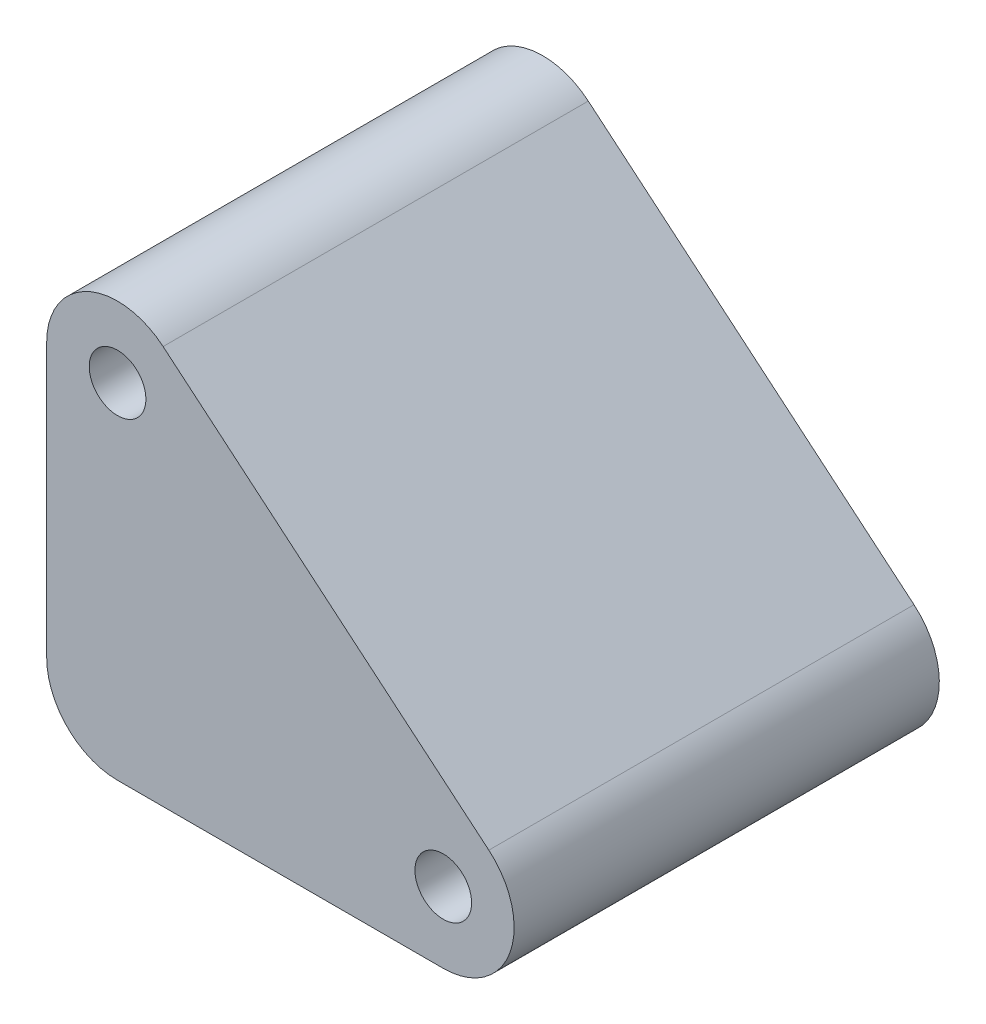
SolidWorks part; units mm, degrees
ref_plane "Front Plane" through (0, 0, 0) normal (0, 0, 1) x (1, 0, 0)
ref_plane "Top Plane" through (0, 0, 0) normal (0, 1, 0) x (1, 0, 0)
ref_plane "Right Plane" through (0, 0, 0) normal (1, 0, 0) x (0, 0, -1)
sketch "Sketch1" plane through (0, 0, 0) normal (0, 0, 1) x (1, 0, 0)
  line L0 (-254.5925, -14.8837) -> (-231.6111, -34.1673)
  line L1 (-234.8251, -42.9975) -> (-257.8064, -42.9975)
  line L2 (-262.8064, -37.9975) -> (-262.8064, -18.7139)
  circle A0 centre (-234.8251, -37.9975) radius 2 construction
  circle A1 centre (-257.8064, -18.7139) radius 2 construction
  circle A2 centre (-234.8251, -37.9975) radius 2
  circle A3 centre (-257.8064, -18.7139) radius 2
  arc A4 (-231.6111, -34.1673) -> (-234.8251, -42.9975) centre (-234.8251, -37.9975) cw
  arc A5 (-257.8064, -42.9975) -> (-262.8064, -37.9975) centre (-257.8064, -37.9975) cw
  arc A6 (-262.8064, -18.7139) -> (-254.5925, -14.8837) centre (-257.8064, -18.7139) cw
  dimension "D1" = 5
  dimension "D2" = 5
  dimension "D3" = 5
  dimension "D4" = 19.2836
  dimension "D5" = 22.9813
extrude "Boss-Extrude1" add sketch "Sketch1" along normal blind 15 and the other way blind 15
